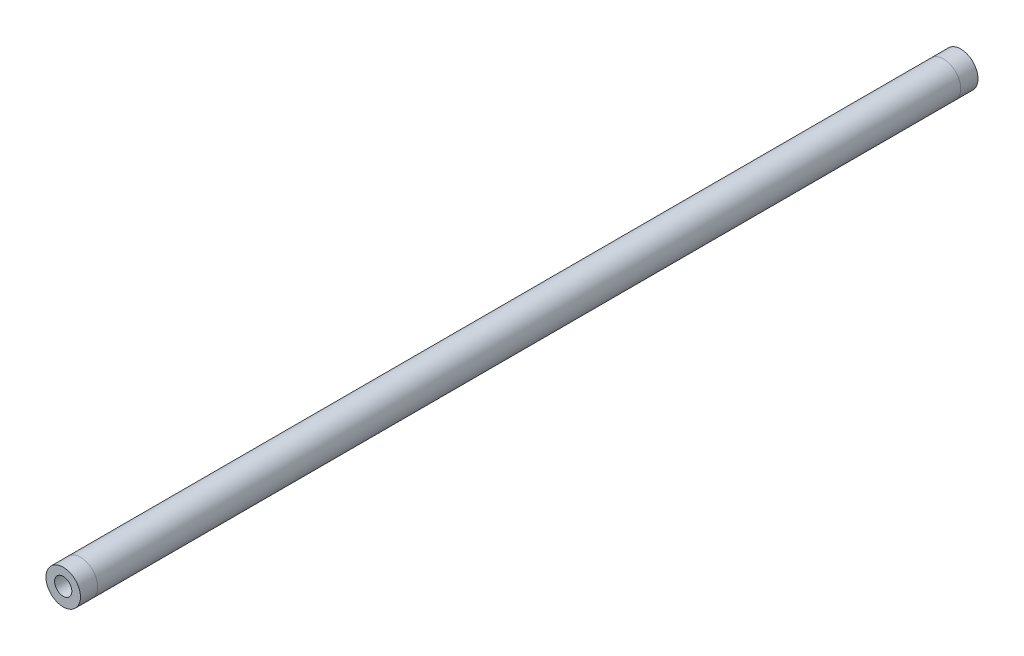
SolidWorks part; units mm, degrees
ref_plane "Front Plane" through (0, 0, 0) normal (0, 0, 1) x (1, 0, 0)
ref_plane "Top Plane" through (0, 0, 0) normal (0, 1, 0) x (1, 0, 0)
ref_plane "Right Plane" through (0, 0, 0) normal (1, 0, 0) x (0, 0, -1)
sketch "Axis" plane through (0, 0, 0) normal (0, 1, 0) x (1, 0, 0)
  line L0 (0, 0) -> (0, 21.8948) construction
  line L1 (0, 21.8948) -> (0, 352.2873) construction
  line L2 (0, 352.2873) -> (0, 374.1821) construction
  dimension "D1" = 21.8948
sketch "Sketch2" plane through (0, 0, 0) normal (0, 0, 1) x (1, 0, 0)
  circle A0 centre (0, 0) radius 6.35
  circle A1 centre (0, 0.235) radius 3.175
  circle A2 centre (0, 0) radius 4.7625
  dimension "D1" = 12.7
  dimension "D2" = 6.35
  dimension "D3" = 9.525
extrude "Threaded Insert 1-1" add sketch "Sketch2" against normal blind 6.35 from vertex contours A0 A2 | A2 A1 region at (-6.1704, 0, 0) region at (-4.6278, 0, 0) starting at point (0, 0, -21.8948)
extrude "Threaded Insert 1-2" add sketch "Sketch2<5>" against normal blind 9.525 from surface contours A2 A1 region at (-4.6278, 0, 0) starting at face at (6.35, 0, -28.2448)
sketch "Sketch2<5>" plane through (0, 0, 0) normal (0, 0, 1) x (1, 0, 0) same geometry as "Sketch2"
extrude "Boss-Extrude4" add sketch "Sketch2<7>" along normal blind 6.35 from vertex separate body contours A0 A2 | A2 A1 region at (-6.1704, 0, 0) region at (-4.6278, 0, 0) starting at point (0, 0, -352.2873)
sketch "Sketch2<7>" plane through (0, 0, 0) normal (0, 0, 1) x (1, 0, 0) same geometry as "Sketch2"
extrude "Boss-Extrude5" add sketch "Sketch2<8>" along normal blind 9.525 from surface contours A2 A1 region at (-4.6278, 0, 0) starting at face at (6.35, 0, -345.9373)
sketch "Sketch2<8>" plane through (0, 0, 0) normal (0, 0, 1) x (1, 0, 0) same geometry as "Sketch2"
extrude "Boss-Extrude6" add sketch "Sketch2<9>" against normal up to surface (345.9373 mm away) from surface separate body contours A0 A2 region at (-6.1704, 0, 0) up to face at (6.35, 0, -345.9373) starting at face at (4.7625, 0, -28.2448)
sketch "Sketch2<9>" plane through (0, 0, 0) normal (0, 0, 1) x (1, 0, 0) same geometry as "Sketch2"
equation "\"Tube Outer Diameter\"= .5"
equation "\"Tube Inner Diameter\"= .375"
equation "\"Rod end Diameter\"= .25"
equation "\"Threaded Insert Out\"= .25"
equation "\"Threaded Insert In\"= .375'`"
equation "\"D1@Sketch2\"=\"Tube Outer Diameter\""
equation "\"D2@Sketch2\"=\"Rod end Diameter\""
equation "\"D1@Threaded Insert 1-1\" = \"Threaded Insert Out\""
equation "\"D3@Sketch2\"=\"Tube Inner Diameter\""
equation "\"D1@Threaded Insert 1-2\" = \"Threaded Insert In\""
equation "\"D1@Boss-Extrude4\"=\"Threaded Insert Out\""
equation "\"D1@Boss-Extrude5\"=\"Threaded Insert In\""
